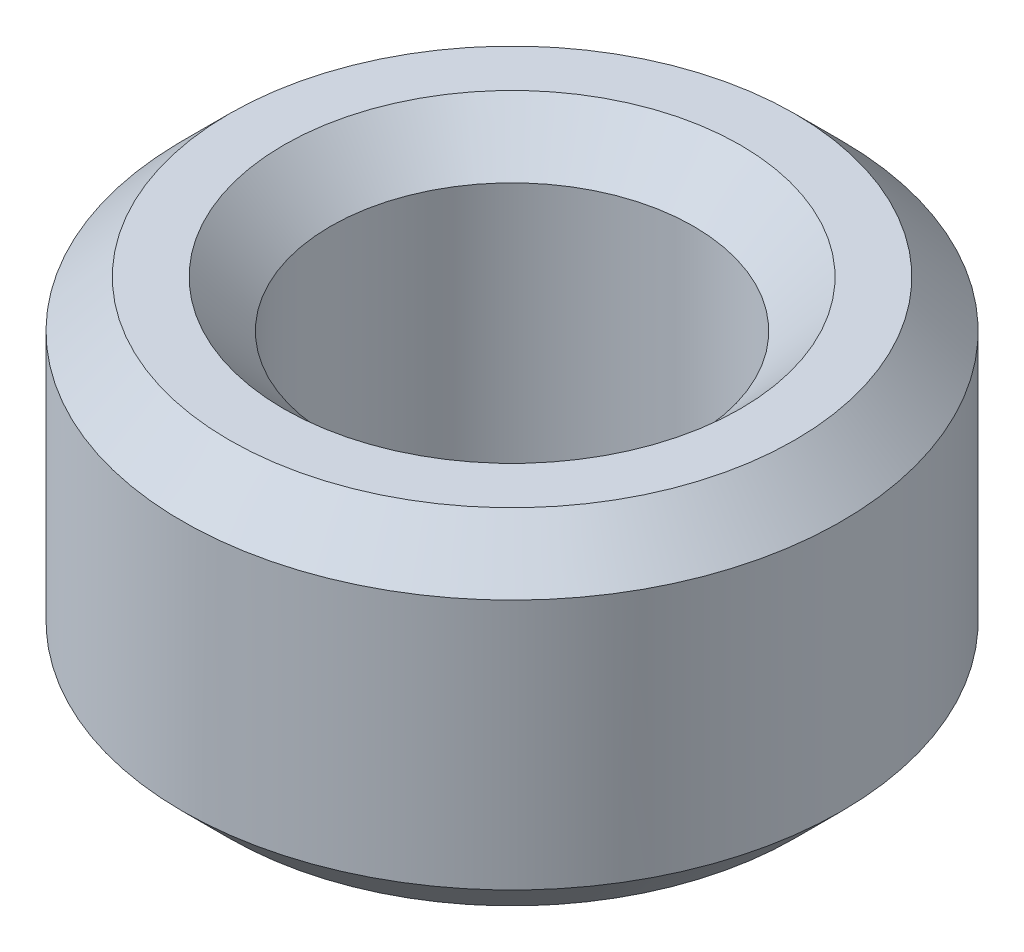
SolidWorks part; units mm, degrees
ref_plane "Front Plane" through (0, 0, 0) normal (0, 0, 1) x (1, 0, 0)
ref_plane "Top Plane" through (0, 0, 0) normal (0, 1, 0) x (1, 0, 0)
ref_plane "Right Plane" through (0, 0, 0) normal (1, 0, 0) x (0, 0, -1)
sketch "Sketch1" plane through (0, 0, 0) normal (0, 1, 0) x (1, 0, 0)
  circle A0 centre (0, 0) radius 12.5
  dimension "SLEEVE_OD" = 25
extrude "Boss-Extrude1" add sketch "Sketch1" along normal blind 13.0782
sketch "Sketch2" plane through (0, 0, 0) normal (0, 1, 0) x (1, 0, 0)
  circle A0 centre (0, 0) radius 6.8849
  dimension "BORE_D" = 13.7699
extrude "Cut-Extrude1" cut sketch "Sketch2" along normal through all
chamfer "Chamfer1" distance 1.778 angle 45 4 edges at (0, 13.0782, 6.8849) (0, 0, 6.8849) (0, 0, 12.5) (0, 13.0782, 12.5)
